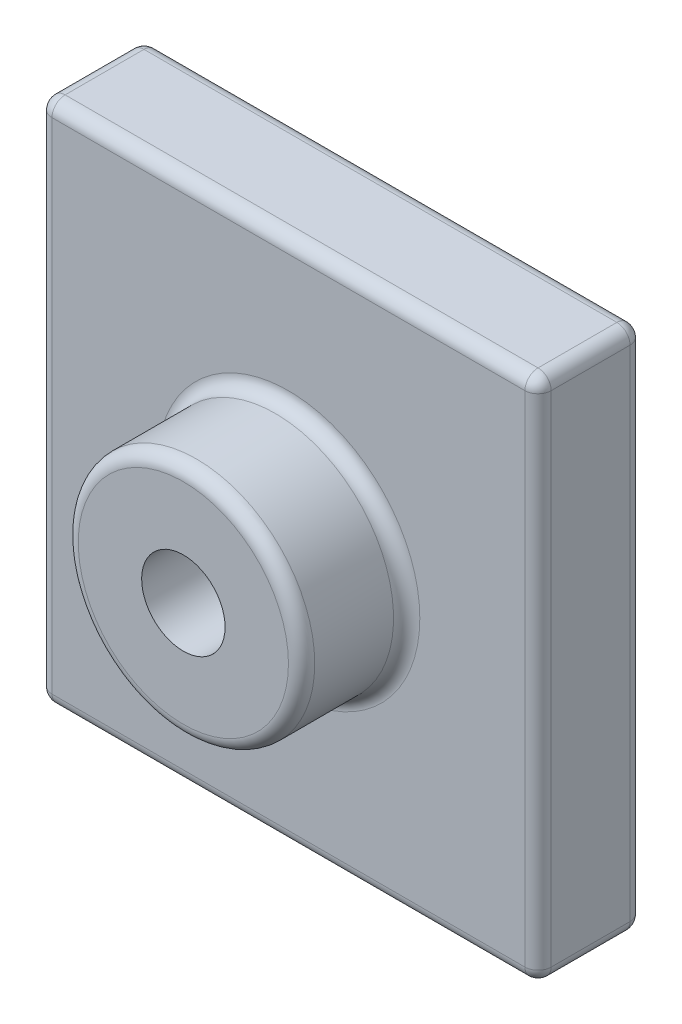
SolidWorks part; units mm, degrees
ref_plane "Front Plane" through (0, 0, 0) normal (0, 0, 1) x (1, 0, 0)
ref_plane "Top Plane" through (0, 0, 0) normal (0, 1, 0) x (1, 0, 0)
ref_plane "Right Plane" through (0, 0, 0) normal (1, 0, 0) x (0, 0, -1)
sketch "Sketch1" plane through (0, 0, 0) normal (0, 0, 1) x (1, 0, 0)
  line L1 (0, 0) -> (38, 0)
  line L2 (0, 0) -> (0, 40)
  line L3 (0, 40) -> (38, 40)
  line L4 (38, 0) -> (38, 40)
  dimension "D1" = 38
  dimension "D2" = 40
extrude "Boss-Extrude1" add sketch "Sketch1" along normal blind 8
sketch "Sketch2" plane through (0, 0, 8) normal (0, 0, 1) x (1, 0, 0)
  line L4 (0, 40) -> (0, 0)
  line L5 (0, 0) -> (38, 0)
  line L6 (38, 0) -> (38, 40)
  line L7 (38, 40) -> (0, 40)
  line L8 (0, 40) -> (0, 0) construction
  line L9 (0, 0) -> (38, 0) construction
  line L10 (38, 0) -> (38, 40) construction
  line L11 (38, 40) -> (0, 40) construction
  circle A0 centre (19, 20) radius 9
  circle A1 centre (19, 20) radius 3.175
  point P2 (19, 20)
  point P4 (0, 20)
  point P6 (19, 0)
  dimension "D2" = 18
  dimension "D3" = 6.35
  dimension "D1" = 0
extrude "Boss-Extrude2" add sketch "Sketch2" along normal blind 8
fillet "Fillet1" radius 1 14 edges at (28, 20, 16) (19, 0, 0) (19, 40, 0) (38, 0, 4) (38, 40, 4) (38, 20, 0) (0, 40, 4) (0, 0, 4) (0, 20, 0) (28, 20, 8) (19, 40, 8) (38, 20, 8) (19, 0, 8) (0, 20, 8)
sketch "Sketch3" plane through (0, 0, 0) normal (0, 0, -1) x (-1, 0, 0)
  line L4 (-1, 39) -> (-37, 39)
  line L5 (-37, 39) -> (-37, 1)
  line L6 (-37, 1) -> (-1, 1)
  line L7 (-1, 1) -> (-1, 39)
  line L8 (-1, 39) -> (-37, 39) construction
  line L9 (-37, 39) -> (-37, 1) construction
  line L10 (-37, 1) -> (-1, 1) construction
  line L11 (-1, 1) -> (-1, 39) construction
  line L15 (-17.1669, 23.175) -> (-20.8331, 23.175)
  line L16 (-20.8331, 23.175) -> (-22.6662, 20)
  line L17 (-22.6662, 20) -> (-20.8331, 16.825)
  line L18 (-20.8331, 16.825) -> (-17.1669, 16.825)
  line L19 (-17.1669, 16.825) -> (-15.3338, 20)
  line L20 (-15.3338, 20) -> (-17.1669, 23.175)
  circle A0 centre (-19, 20) radius 3.175 construction
  point P2 (-19, 39)
  point P4 (-37, 20)
  point P6 (-19, 20)
  dimension "D2" = 6.35
  dimension "D1" = 0
extrude "Cut-Extrude1" cut sketch "Sketch3" against normal blind 5.5562
sketch "Sketch4" plane through (0, 0, 0) normal (0, 0, -1) x (-1, 0, 0)
  circle A0 centre (-19, 20) radius 3.175 construction
  circle A1 centre (-19, 20) radius 3.175
extrude "Cut-Extrude2" cut sketch "Sketch4" against normal through all
